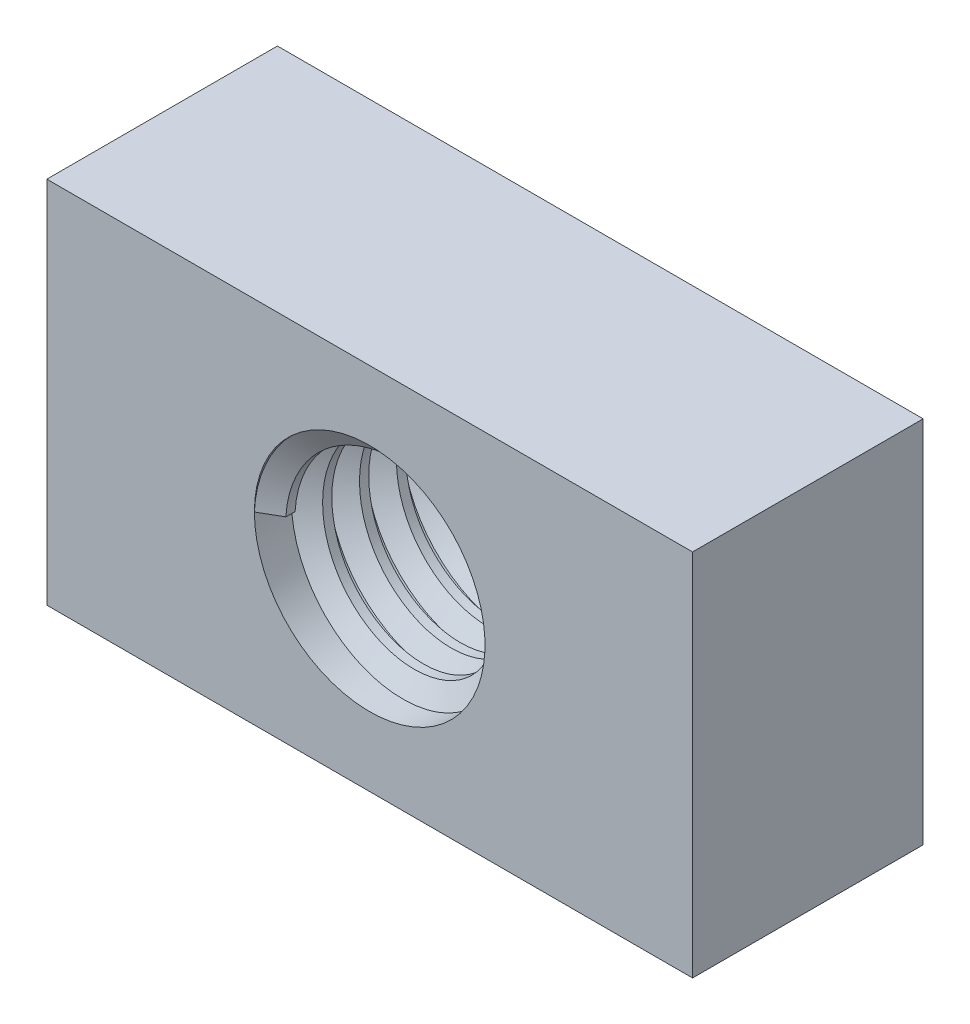
SolidWorks part; units mm, degrees
ref_plane "Front Plane" through (0, 0, 0) normal (0, 0, 1) x (1, 0, 0)
ref_plane "Top Plane" through (0, 0, 0) normal (0, 1, 0) x (1, 0, 0)
ref_plane "Right Plane" through (0, 0, 0) normal (1, 0, 0) x (0, 0, -1)
sketch "Sketch1" plane through (0, 0, 0) normal (0, 0, 1) x (1, 0, 0)
  line L1 (0, 0) -> (14, 0)
  line L2 (0, 0) -> (0, 8)
  line L3 (0, 8) -> (14, 8)
  line L4 (14, 0) -> (14, 8)
  circle A0 centre (7, 4) radius 2.5
  dimension "D3" = 5
  dimension "D1" = 8
  dimension "D2" = 14
  dimension "D4" = 4
  dimension "D5" = 7
extrude "Boss-Extrude1" add sketch "Sketch1" along normal blind 5
thread "Thread1" pitch 0.8 method extrude profile "Thread Profile1" start angle 0, offset 0, length 4.5, pitch 0.8, diameter 5
ref_plane "Plane1" through (4.5, 4, 5) normal (0, -1, 0) x (-1, 0, 0)
sketch "Thread Profile1" plane through (4.5, 4, 5) normal (0, -1, 0) x (-1, 0, 0)
  line L0 (0, 0) -> (0, 0.8) construction
  line L11 (0, 0) -> (0, 0.7)
  line L12 (0, 0.7) -> (-0.433, 0.45)
  line L13 (-0.433, 0.45) -> (-0.433, 0.25)
  line L15 (-0.433, 0.25) -> (0, 0)
  line L17 (-0.433, 0.35) -> (0, 0.35) construction
  point P2 (0, 0)
  dimension "Pitch" = 0.8
  dimension "Profile_Angle" = 60
  dimension "Profile_Land" = 0.2
  dimension "Profile_Height" = 0.433
